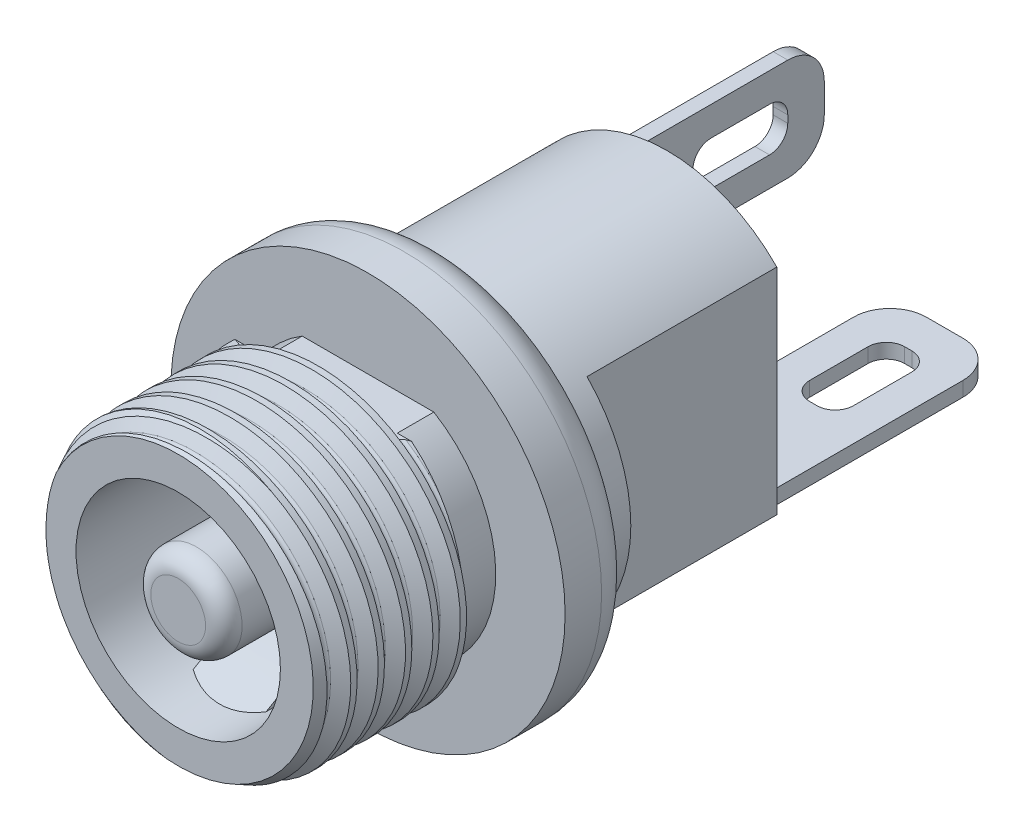
SolidWorks part; units mm, degrees
ref_plane "Спереди" through (0, 0, 0) normal (0, 0, 1) x (1, 0, 0)
ref_plane "Сверху" through (0, 0, 0) normal (0, 1, 0) x (1, 0, 0)
ref_plane "Справа" through (0, 0, 0) normal (1, 0, 0) x (0, 0, -1)
sketch "Эскиз1" plane through (0, 0, 0) normal (0, 0, 1) x (1, 0, 0)
  circle A0 centre (0, 0) radius 5.4
  dimension "D1" = 10.8
extrude "Бобышка-Вытянуть1" add sketch "Эскиз1" against normal blind 2
sketch "Эскиз2" plane through (0, 0, 0) normal (0, 0, 1) x (1, 0, 0)
  circle A0 centre (0, 0) radius 3.5
  dimension "D1" = 7
extrude "Бобышка-Вытянуть2" add sketch "Эскиз2" along normal blind 1
sketch "Эскиз15" plane through (0, 0, 1) normal (0, 0, 1) x (1, 0, 0)
  circle A0 centre (0, 0) radius 4
  dimension "D1" = 8
extrude "Бобышка-Вытянуть8" add sketch "Эскиз15" along normal blind 4.2
sketch "Эскиз3" plane through (0, 0, -2) normal (0, 0, -1) x (-1, 0, 0)
  circle A0 centre (0, 0) radius 4.2
  dimension "D1" = 8.4
extrude "Бобышка-Вытянуть3" add sketch "Эскиз3" along normal blind 6.2
sketch "Эскиз4" plane through (0, 0, 0) normal (1, 0, 0) x (0, 0, -1)
  line L0 (8.2, 1) -> (8.6, 1)
  line L1 (8.2, -4.2) -> (8.2, 4.2) construction
  line L2 (8.6, 1) -> (8.6, -2.8)
  line L3 (9.6, -3.8) -> (15.8, -3.8)
  line L4 (15.8, -3.8) -> (15.8, -4.2)
  line L5 (15.8, -4.2) -> (9.6, -4.2)
  line L6 (8.2, -2.8) -> (8.2, 1)
  line L8 (-5.2, 4) -> (-5.2, -4) construction
  arc A0 (8.6, -2.8) -> (9.6, -3.8) centre (9.6, -2.8) ccw
  arc A1 (9.6, -4.2) -> (8.2, -2.8) centre (9.6, -2.8) cw
  point P15 (8.2, -4.2)
  dimension "D6" = 1
  dimension "D7" = 1.4
  dimension "D1" = 0.4
  dimension "D2" = 0.4
  dimension "D3" = 1
  dimension "D4" = 4.2
  dimension "D5" = 21
extrude "Бобышка-Вытянуть4" add sketch "Эскиз4" along normal blind 1.5 and the other way blind 1.5
sketch "Эскиз12" plane through (0, 0, -8.6) normal (0, 0, -1) x (-1, 0, 0)
  circle A0 centre (0, 0) radius 0.75
  dimension "D1" = 1.5
extrude "Бобышка-Вытянуть7" add sketch "Эскиз12" along normal blind 0.4
sketch "Эскиз5" plane through (0, -3.8, 0) normal (0, 1, 0) x (1, 0, 0)
  line L0 (-1.5, 15.8) -> (1.5, 15.8) construction
  line L1 (-0.1, 14.8) -> (0.1, 14.8)
  line L2 (-0.6, 14.3) -> (-0.6, 12.7)
  line L3 (-0.1, 12.2) -> (0.1, 12.2)
  line L4 (0.6, 14.3) -> (0.6, 12.7)
  line L5 (-0.6, 14.8) -> (0.6, 12.2) construction
  line L6 (-0.6, 12.2) -> (0.6, 14.8) construction
  arc A0 (0.1, 12.2) -> (0.6, 12.7) centre (0.1, 12.7) ccw
  arc A1 (-0.6, 12.7) -> (-0.1, 12.2) centre (-0.1, 12.7) ccw
  arc A2 (0.1, 14.8) -> (0.6, 14.3) centre (0.1, 14.3) cw
  arc A3 (-0.1, 14.8) -> (-0.6, 14.3) centre (-0.1, 14.3) ccw
  point P0 (0, 13.5)
  dimension "D5" = 0.5
  dimension "D1" = 0
  dimension "D2" = 1.2
  dimension "D3" = 2.6
  dimension "D4" = 1
extrude "Вырез-Вытянуть1" cut sketch "Эскиз5" against normal blind 1.5
sketch "Эскиз10" plane through (0, 0, 0) normal (0, 1, 0) x (1, 0, 0)
  line L5 (-3.7, 15.8) -> (-3.3, 15.8)
  line L6 (-3.7, 15.8) -> (-3.7, 7.8)
  line L7 (-3.7, 7.8) -> (-3.3, 7.8)
  line L8 (-3.3, 15.8) -> (-3.3, 7.8)
  line L9 (-3.7, 15.8) -> (-3.3, 7.8) construction
  line L10 (-3.7, 7.8) -> (-3.3, 15.8) construction
  line L11 (-4, -5.2) -> (4, -5.2) construction
  point P0 (-3.5, 11.8)
  dimension "D1" = 3.5
  dimension "D2" = 0.4
  dimension "D3" = 21
  dimension "D4" = 8
extrude "Бобышка-Вытянуть6" add sketch "Эскиз10" along normal blind 1.4 and the other way blind 1.4
sketch "Эскиз11" plane through (-3.7, 0, 0) normal (-1, 0, 0) x (0, 0, 1)
  line L0 (-15.8, 1.4) -> (-8.2, 1.4) construction
  line L1 (-14.3, 0.6) -> (-12.7, 0.6)
  line L2 (-14.8, 0.1) -> (-14.8, -0.1)
  line L3 (-14.3, -0.6) -> (-12.7, -0.6)
  line L4 (-12.2, 0.1) -> (-12.2, -0.1)
  line L5 (-14.8, 0.6) -> (-12.2, -0.6) construction
  line L6 (-14.8, -0.6) -> (-12.2, 0.6) construction
  line L7 (-15.8, -1.4) -> (-15.8, 1.4) construction
  arc A0 (-12.7, 0.6) -> (-12.2, 0.1) centre (-12.7, 0.1) cw
  arc A1 (-12.7, -0.6) -> (-12.2, -0.1) centre (-12.7, -0.1) ccw
  arc A2 (-14.8, -0.1) -> (-14.3, -0.6) centre (-14.3, -0.1) ccw
  arc A3 (-14.3, 0.6) -> (-14.8, 0.1) centre (-14.3, 0.1) ccw
  point P0 (-13.5, 0)
  dimension "D5" = 0.5
  dimension "D1" = 1.4
  dimension "D2" = 2.6
  dimension "D3" = 1.2
  dimension "D4" = 1
extrude "Вырез-Вытянуть4" cut sketch "Эскиз11" against normal blind 1.4
fillet "Скругление1" radius 1 6 edges at (-1.5, 1, -8.4) (1.5, 1, -8.4) (-1.5, -4, -15.8) (1.5, -4, -15.8) (-3.5, -1.4, -15.8) (-3.5, 1.4, -15.8)
fillet "Скругление3" radius 1 1 edges at (5.4, 0, -2)
sketch "Эскиз6" plane through (0, 0, 0) normal (1, 0, 0) x (0, 0, -1)
  line L0 (0, 3.5) -> (0, -3.5) construction
  line L1 (-1.25, 5.4) -> (0, 5.4)
  line L2 (-1.25, 5.4) -> (-1.25, 3)
  line L3 (-1.25, 3) -> (0, 3)
  line L4 (0, 5.4) -> (0, 3)
  dimension "D1" = 1.25
  dimension "D2" = 5.4
  dimension "D3" = 3
extrude "Вырез-Вытянуть2" cut sketch "Эскиз6" against normal through all both and the other way through all
sketch "Эскиз16" plane through (0, 0, 5.2) normal (0, 0, 1) x (1, 0, 0)
  circle A0 centre (0, 0) radius 2.8
  dimension "D1" = 5.6
extrude "Вырез-Вытянуть5" cut sketch "Эскиз16" against normal blind 6
sketch "Эскиз17" plane through (0, 0, -0.8) normal (0, 0, 1) x (1, 0, 0)
  circle A0 centre (0, 0) radius 1.25
  dimension "D1" = 2.5
extrude "Бобышка-Вытянуть9" add sketch "Эскиз17" along normal blind 6
fillet "Скругление4" radius 0.5 1 edges at (1.25, 0, 5.2)
sketch "Эскиз18" plane through (0, 0, 0) normal (0, 1, 0) x (1, 0, 0)
  line L1 (6, 10) -> (3, 10)
  line L2 (6, 10) -> (6, 3)
  line L3 (6, 3) -> (3, 3)
  line L4 (3, 10) -> (3, 3)
  dimension "D1" = 3
  dimension "D2" = 3
  dimension "D3" = 3
  dimension "D4" = 7
extrude "Вырез-Вытянуть6" cut sketch "Эскиз18" against normal through all both and the other way through all
sketch "Эскиз20" plane through (0, 0, 0) normal (1, 0, 0) x (0, 0, -1)
  line L0 (-1, -2) -> (0, -2)
  spline S0 degree 2 poles (-4, -3) (-2.653, -2.0103) (-1, -2) knots 0 0 0 1 1 1
  dimension "D3" = 2.4
  dimension "D1" = 3
  dimension "D2" = 4
  dimension "D4" = 0
  dimension "D5" = 1
  dimension "D6" = 2.2
  dimension "D7" = 2
sketch "Эскиз21" plane through (0, 0, 0) normal (0, 0, 1) x (1, 0, 0)
  line L1 (-1, -1.8) -> (1, -1.8)
  line L2 (-1, -1.8) -> (-1, -2.2)
  line L3 (-1, -2.2) -> (1, -2.2)
  line L4 (1, -1.8) -> (1, -2.2)
  line L5 (-1, -1.8) -> (1, -2.2) construction
  line L6 (-1, -2.2) -> (1, -1.8) construction
  point P0 (0, -2)
  dimension "D1" = 0
  dimension "D2" = 2
  dimension "D3" = 0.4
  dimension "D4" = 2
sweep "По траектории1" add profiles "Эскиз21" path "Эскиз20"
chamfer "Фаска1" distance 0.6 distance2 0.3 1 edges at (4, 0, 5.2) first distance on face at (4, 0, 5.2)
ref_plane "Плоскость1" through (0, 0, 7.2) normal (0, 0, 1) x (1, 0, 0)
sketch "Эскиз13" plane through (0, 0, 0) normal (1, 0, 0) x (0, 0, -1)
  line L8 (-7.7774, 4.5) -> (-7.2866, 3.65)
  line L9 (-7.1134, 3.65) -> (-6.6226, 4.5)
  line L10 (-6.6226, 4.5) -> (-6.6226, 4.7)
  line L11 (-6.6226, 4.7) -> (-7.7774, 4.7)
  line L12 (-7.7774, 4.7) -> (-7.7774, 4.5)
  line L13 (-7.2, 3.5) -> (-7.2, 4.8622) construction
  arc A0 (-7.2866, 3.65) -> (-7.1134, 3.65) centre (-7.2, 3.7) ccw
  dimension "D5" = 0.1
  dimension "D1" = 30
  dimension "D2" = 30
  dimension "D3" = 1
  dimension "D4" = 1
  dimension "D6" = 0.2
  dimension "D7" = 0.2
  dimension "D8" = 1.1547
  dimension "D9" = 7.2
  dimension "D10" = 3.5
sketch "Эскиз14" plane through (0, 0, 7.2) normal (0, 0, 1) x (1, 0, 0)
  circle A0 centre (0, 0) radius 3.5
  dimension "D1" = 7
curve "Спираль1" pitch 0.75 height 6.375 radius 3.5 centre (0, 0, 7.2) axis (0, 0, -1) start towards (0, 1, 0)
sweep "Вырез-По траектории1" cut profiles "Эскиз13" path "Спираль1" align with end faces yes
